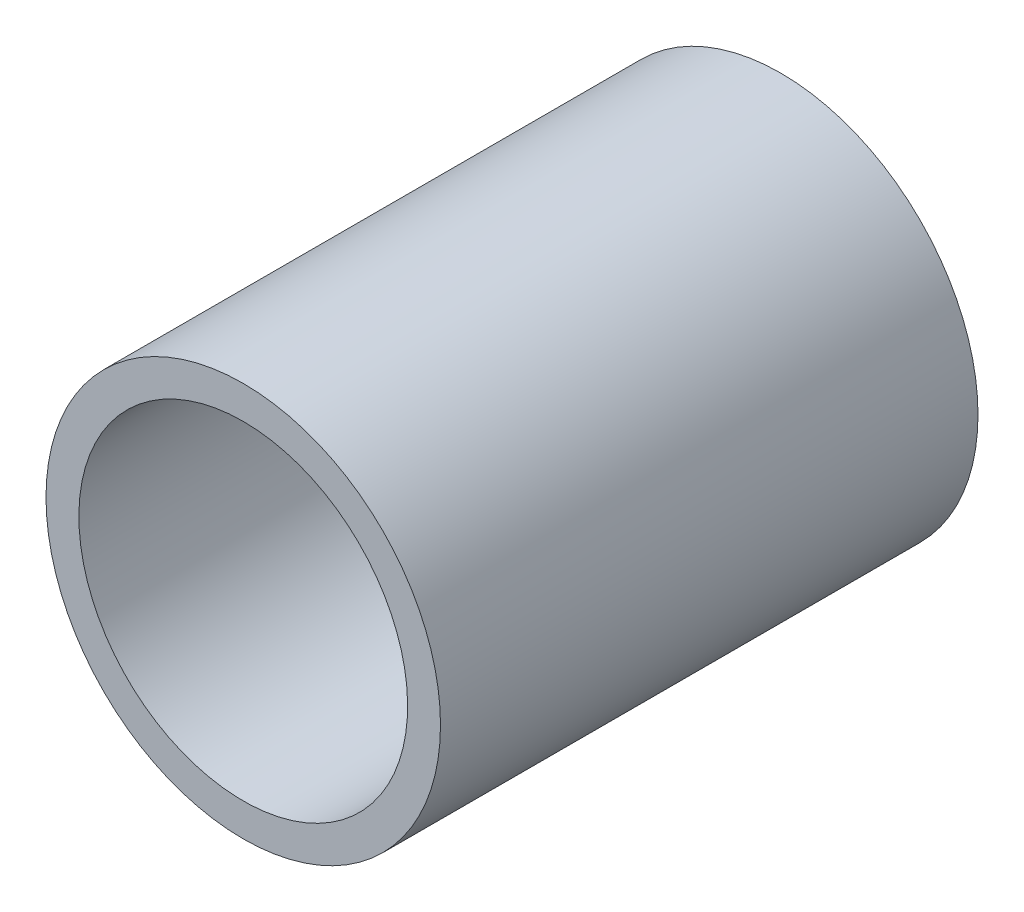
SolidWorks part; units mm, degrees
material "PLA 50%"
ref_plane "Front Plane" through (0, 0, 0) normal (0, 0, 1) x (1, 0, 0)
ref_plane "Top Plane" through (0, 0, 0) normal (0, 1, 0) x (1, 0, 0)
ref_plane "Right Plane" through (0, 0, 0) normal (1, 0, 0) x (0, 0, -1)
ref_axis "X" through (-88.99, 0, 0) along (1, 0, 0)
ref_axis "Y" through (0, 55, 0) along (0, -1, 0)
ref_axis "Z" through (0, 0, -88.99) along (0, 0, 1)
sketch "Sketch1" plane through (0, 0, 0) normal (0, 0, 1) x (1, 0, 0)
  circle A0 centre (0, 0) radius 5
  circle A1 centre (0, 0) radius 6
  dimension "D1" = 10
  dimension "D2" = 12
extrude "Boss-Extrude1" add sketch "Sketch1" along normal up to surface (16.35 mm away)
